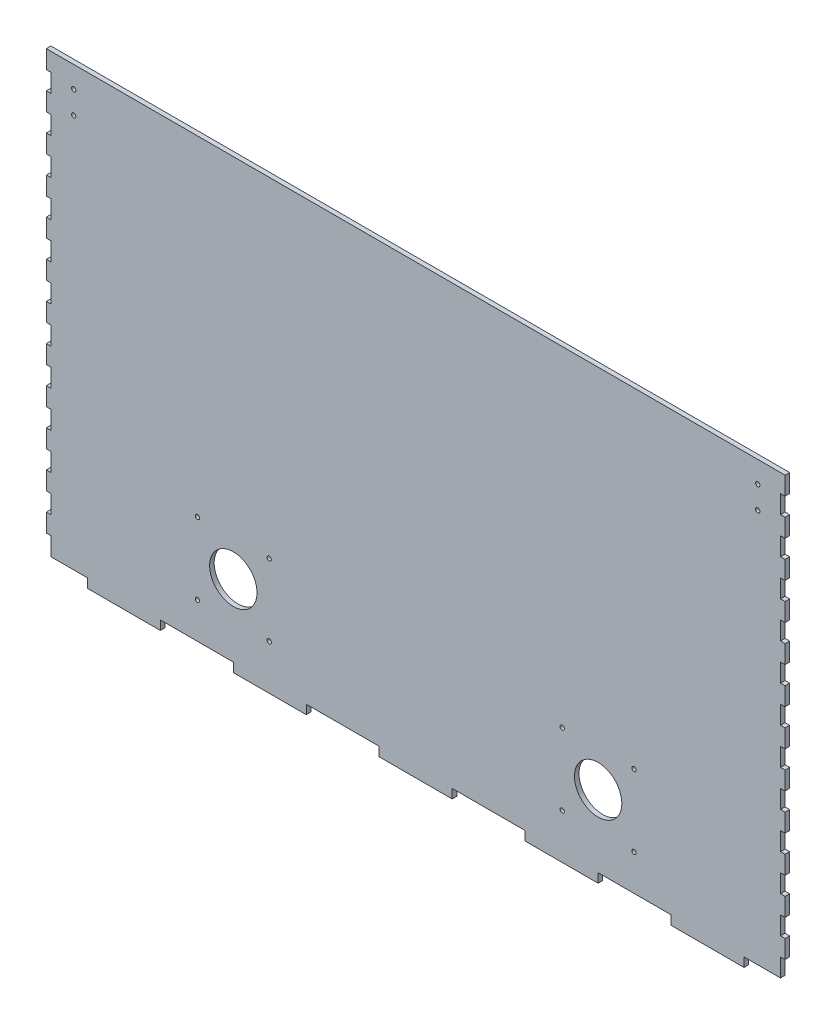
SolidWorks part; units mm, degrees
ref_plane "Front Plane" through (0, 0, 0) normal (0, 0, 1) x (1, 0, 0)
ref_plane "Top Plane" through (0, 0, 0) normal (0, 1, 0) x (1, 0, 0)
ref_plane "Right Plane" through (0, 0, 0) normal (1, 0, 0) x (0, 0, -1)
sketch "Sketch1" plane through (0, 0, 0) normal (0, 0, 1) x (1, 0, 0)
  line L0 (0, 0) -> (508, 0)
  line L1 (508, 0) -> (508, 304.8)
  line L2 (508, 304.8) -> (0, 304.8)
  line L3 (0, 304.8) -> (0, 0)
  line L4 (254, 304.8) -> (254, 0) construction
  line L5 (0, 304.8) -> (-3.175, 304.8)
  line L6 (-3.175, 304.8) -> (-3.175, 292.1)
  line L7 (-3.175, 292.1) -> (0, 292.1)
  line L8 (25.4, 0) -> (25.4, -6.35)
  line L9 (25.4, -6.35) -> (76.2, -6.35)
  line L10 (76.2, -6.35) -> (76.2, 0)
  line L13 (0, 279.4) -> (-3.175, 279.4)
  line L14 (-3.175, 279.4) -> (-3.175, 266.7)
  line L15 (-3.175, 266.7) -> (0, 266.7)
  line L17 (0, 254) -> (-3.175, 254)
  line L18 (-3.175, 254) -> (-3.175, 241.3)
  line L19 (-3.175, 241.3) -> (0, 241.3)
  line L21 (0, 228.6) -> (-3.175, 228.6)
  line L22 (-3.175, 228.6) -> (-3.175, 215.9)
  line L23 (-3.175, 215.9) -> (0, 215.9)
  line L25 (0, 203.2) -> (-3.175, 203.2)
  line L26 (-3.175, 203.2) -> (-3.175, 190.5)
  line L27 (-3.175, 190.5) -> (0, 190.5)
  line L29 (0, 177.8) -> (-3.175, 177.8)
  line L30 (-3.175, 177.8) -> (-3.175, 165.1)
  line L31 (-3.175, 165.1) -> (0, 165.1)
  line L33 (0, 152.4) -> (-3.175, 152.4)
  line L34 (-3.175, 152.4) -> (-3.175, 139.7)
  line L35 (-3.175, 139.7) -> (0, 139.7)
  line L37 (0, 127) -> (-3.175, 127)
  line L38 (-3.175, 127) -> (-3.175, 114.3)
  line L39 (-3.175, 114.3) -> (0, 114.3)
  line L41 (0, 101.6) -> (-3.175, 101.6)
  line L42 (-3.175, 101.6) -> (-3.175, 88.9)
  line L43 (-3.175, 88.9) -> (0, 88.9)
  line L45 (0, 76.2) -> (-3.175, 76.2)
  line L46 (-3.175, 76.2) -> (-3.175, 63.5)
  line L47 (-3.175, 63.5) -> (0, 63.5)
  line L49 (0, 50.8) -> (-3.175, 50.8)
  line L50 (-3.175, 50.8) -> (-3.175, 38.1)
  line L51 (-3.175, 38.1) -> (0, 38.1)
  line L53 (0, 25.4) -> (-3.175, 25.4)
  line L54 (-3.175, 25.4) -> (-3.175, 12.7)
  line L55 (-3.175, 12.7) -> (0, 12.7)
  line L57 (0, 304.8) -> (0, 279.4) construction
  line L59 (127, 0) -> (127, -6.35)
  line L60 (127, -6.35) -> (177.8, -6.35)
  line L61 (177.8, -6.35) -> (177.8, 0)
  line L63 (228.6, 0) -> (228.6, -6.35)
  line L64 (228.6, -6.35) -> (279.4, -6.35)
  line L65 (279.4, -6.35) -> (279.4, 0)
  line L67 (330.2, 0) -> (330.2, -6.35)
  line L68 (330.2, -6.35) -> (381, -6.35)
  line L69 (381, -6.35) -> (381, 0)
  line L70 (76.2, 0) -> (177.8, 0) construction
  line L72 (431.8, 0) -> (431.8, -6.35)
  line L73 (431.8, -6.35) -> (482.6, -6.35)
  line L74 (482.6, -6.35) -> (482.6, 0)
  line L76 (511.175, 12.7) -> (508, 12.7)
  line L77 (511.175, 25.4) -> (511.175, 12.7)
  line L78 (508, 25.4) -> (511.175, 25.4)
  line L80 (511.175, 38.1) -> (508, 38.1)
  line L81 (511.175, 50.8) -> (511.175, 38.1)
  line L82 (508, 50.8) -> (511.175, 50.8)
  line L84 (511.175, 63.5) -> (508, 63.5)
  line L85 (511.175, 76.2) -> (511.175, 63.5)
  line L86 (508, 76.2) -> (511.175, 76.2)
  line L88 (511.175, 88.9) -> (508, 88.9)
  line L89 (511.175, 101.6) -> (511.175, 88.9)
  line L90 (508, 101.6) -> (511.175, 101.6)
  line L92 (511.175, 114.3) -> (508, 114.3)
  line L93 (511.175, 127) -> (511.175, 114.3)
  line L94 (508, 127) -> (511.175, 127)
  line L96 (511.175, 139.7) -> (508, 139.7)
  line L97 (511.175, 152.4) -> (511.175, 139.7)
  line L98 (508, 152.4) -> (511.175, 152.4)
  line L100 (511.175, 165.1) -> (508, 165.1)
  line L101 (511.175, 177.8) -> (511.175, 165.1)
  line L102 (508, 177.8) -> (511.175, 177.8)
  line L104 (511.175, 190.5) -> (508, 190.5)
  line L105 (511.175, 203.2) -> (511.175, 190.5)
  line L106 (508, 203.2) -> (511.175, 203.2)
  line L108 (511.175, 215.9) -> (508, 215.9)
  line L109 (511.175, 228.6) -> (511.175, 215.9)
  line L110 (508, 228.6) -> (511.175, 228.6)
  line L112 (511.175, 241.3) -> (508, 241.3)
  line L113 (511.175, 254) -> (511.175, 241.3)
  line L114 (508, 254) -> (511.175, 254)
  line L116 (511.175, 266.7) -> (508, 266.7)
  line L117 (511.175, 279.4) -> (511.175, 266.7)
  line L118 (508, 279.4) -> (511.175, 279.4)
  line L120 (511.175, 292.1) -> (508, 292.1)
  line L121 (511.175, 304.8) -> (511.175, 292.1)
  line L122 (508, 304.8) -> (511.175, 304.8)
  dimension "D1" = 508
  dimension "D2" = 304.8
  dimension "D3" = 3.175
  dimension "D4" = 12.7
  dimension "D5" = 6.35
  dimension "D6" = 50.8
  dimension "D7" = 25.4
  dimension "D9" = 25.4
  dimension "D11" = 101.6
  dimension "D8" = 12
  dimension "D10" = 5
extrude "Boss-Extrude1" add sketch "Sketch1" along normal blind 3.175 contours L2 L3 L0 L1 | L9 L10 L0 L8 | L60 L61 L0 L59 | L64 L65 L0 L63 | L68 L69 L0 L67 | L73 L74 L0 L72 | L54 L55 L3 L53 | L50 L51 L3 L49 | L46 L47 L3 L45 | L42 L43 L3 L41 | L38 L39 L3 L37 | L34 L35 L3 L33 | L30 L31 L3 L29 | L26 L27 L3 L25 | L22 L23 L3 L21 | L18 L19 L3 L17 | L14 L15 L3 L13 | L6 L7 L3 L5 | L78 L1 L76 L77 | L82 L1 L80 L81 | L86 L1 L84 L85 | L90 L1 L88 L89 | L98 L1 L96 L97 | L94 L1 L92 L93 | L102 L1 L100 L101 | L106 L1 L104 L105 | L110 L1 L108 L109 | L114 L1 L112 L113 | L118 L1 L116 L117 | L122 L1 L120 L121 region at (254, 152.4, 0) region at (50.8, -3.175, 0) region at (-1.5875, 19.05, 0) region at (152.4, -3.175, 0) region at (-1.5875, 44.45, 0) region at (254, -3.175, 0) region at (-1.5875, 69.85, 0) region at (355.6, -3.175, 0) region at (-1.5875, 95.25, 0) region at (457.2, -3.175, 0) region at (-1.5875, 120.65, 0) region at (-1.5875, 146.05, 0) region at (509.5875, 19.05, 0) region at (-1.5875, 171.45, 0) region at (509.5875, 44.45, 0) region at (-1.5875, 196.85, 0) region at (509.5875, 69.85, 0) region at (-1.5875, 222.25, 0) region at (509.5875, 95.25, 0) region at (-1.5875, 247.65, 0) region at (509.5875, 120.65, 0) region at (-1.5875, 273.05, 0) region at (509.5875, 146.05, 0) region at (-1.5875, 298.45, 0) region at (509.5875, 171.45, 0) region at (509.5875, 298.45, 0) region at (509.5875, 196.85, 0) region at (509.5875, 273.05, 0) region at (509.5875, 222.25, 0) region at (509.5875, 247.65, 0)
sketch "Sketch2" plane through (0, 0, 3.175) normal (0, 0, 1) x (1, 0, 0)
  line L0 (254, 304.8) -> (254, -6.35) construction
  line L1 (511.175, 304.8) -> (-3.175, 304.8) construction
  line L2 (228.6, -6.35) -> (279.4, -6.35) construction
  line L3 (0, 6.35) -> (254, 6.35) construction
  line L5 (0, 12.7) -> (0, 0) construction
  line L6 (127, 6.35) -> (127, 304.8) construction
  line L7 (110.5, 50) -> (143.5, 50) construction
  line L8 (76.2, 0) -> (127, 0) construction
  circle A0 centre (127, 50) radius 16.5
  circle A1 centre (102, 75) radius 1.5
  circle A2 centre (152, 75) radius 1.5
  circle A3 centre (152, 25) radius 1.5
  circle A4 centre (102, 25) radius 1.5
  circle A5 centre (381, 50) radius 16.5
  circle A6 centre (356, 75) radius 1.5
  circle A7 centre (356, 25) radius 1.5
  circle A8 centre (406, 25) radius 1.5
  circle A9 centre (406, 75) radius 1.5
  dimension "D1" = 33
  dimension "D2" = 3
  dimension "D3" = 25
  dimension "D4" = 25
  dimension "D5" = 50
extrude "Cut-Extrude1" cut sketch "Sketch2" against normal up to surface (3.175 mm away) up to face at (254, 125.5767, 0)
sketch "Sketch3" plane through (0, 0, 3.175) normal (0, 0, 1) x (1, 0, 0)
  line L1 (511.175, 304.8) -> (-3.175, 304.8) construction
  line L2 (254, 304.8) -> (254, -6.35) construction
  line L3 (228.6, -6.35) -> (279.4, -6.35) construction
  line L4 (-3.175, 304.8) -> (-3.175, 292.1) construction
  circle A0 centre (15.875, 289.8) radius 1.5
  circle A1 centre (15.875, 274.05) radius 1.5
  circle A2 centre (492.125, 289.8) radius 1.5
  circle A3 centre (492.125, 274.05) radius 1.5
  dimension "D1" = 3
  dimension "D2" = 3
  dimension "D3" = 19.05
  dimension "D4" = 15.75
  dimension "D5" = 15
extrude "Cut-Extrude2" cut sketch "Sketch3" against normal up to surface (3.175 mm away) up to face at (103.5, 75, 0)
equation "\"wall_thickness\"= 0.125in"
equation "\"base_thickness\"= 0.25in"
equation "\"D3@Sketch1\"=\"wall_thickness\""
equation "\"D5@Sketch1\"=\"base_thickness\""
equation "\"D1@Boss-Extrude1\"=\"wall_thickness\""
